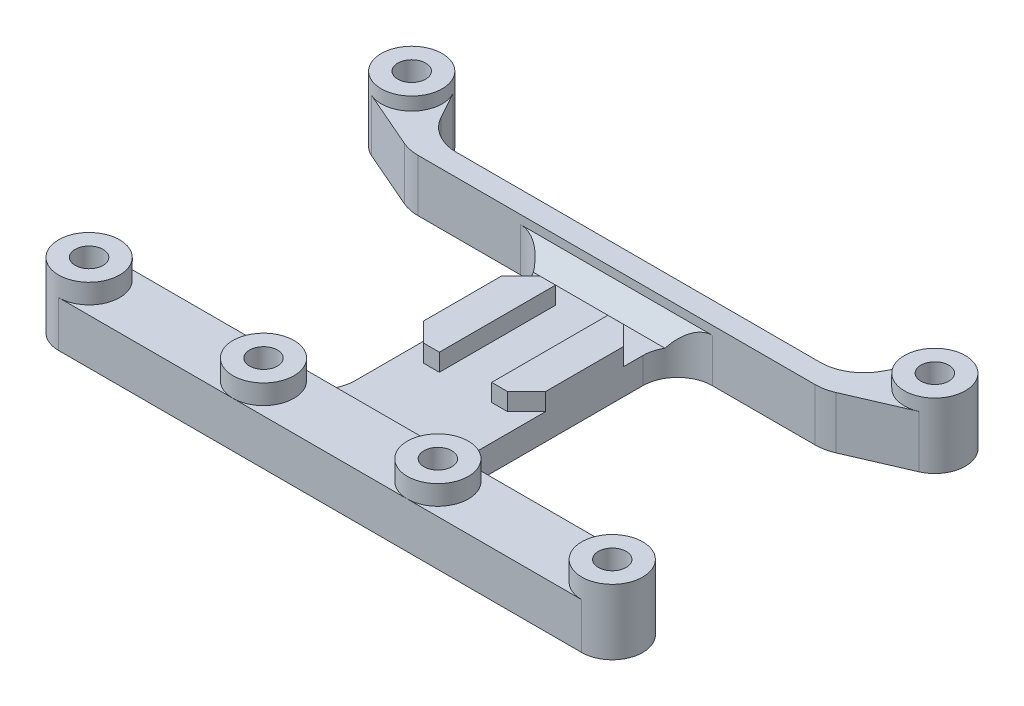
SolidWorks part; units mm, degrees
ref_plane "Front Plane" through (0, 0, 0) normal (0, 0, 1) x (1, 0, 0)
ref_plane "Top Plane" through (0, 0, 0) normal (0, 1, 0) x (1, 0, 0)
ref_plane "Right Plane" through (0, 0, 0) normal (1, 0, 0) x (0, 0, -1)
sketch "Sketch1" plane through (0, 0, 0) normal (0, 1, 0) x (1, 0, 0)
  line L3 (0, 3.5) -> (0, 33) construction
  line L4 (30, 3.5) -> (11, 3.5)
  line L5 (-30, -3.5) -> (30, -3.5)
  line L6 (-20.8493, 33.0006) -> (20.8488, 33)
  line L7 (7, 7.5) -> (7, 26.5002)
  line L8 (-7, 7.5) -> (-7, 26.5005)
  line L9 (-22.7685, 30.5006) -> (-10.9999, 30.5005)
  line L10 (-25.2301, 35.5907) -> (-26.9334, 38.687)
  line L11 (-24.7567, 30.913) -> (-31.3917, 33.7886)
  line L12 (24.7553, 30.9124) -> (31.3917, 33.7886)
  line L13 (25.2298, 35.5901) -> (26.9334, 38.687)
  line L14 (11.0001, 30.5002) -> (22.7669, 30.5)
  line L15 (-11, 3.5) -> (-30, 3.5)
  circle A2 centre (-30, 0) radius 1.6
  circle A3 centre (-10, 0) radius 1.6
  circle A4 centre (10, 0) radius 1.6
  circle A5 centre (30, 0) radius 1.6
  arc A6 (-26.9334, 38.687) -> (-31.3917, 33.7886) centre (-30, 37) ccw
  arc A7 (30, -3.5) -> (30, 3.5) centre (30, 0) ccw
  arc A8 (-30, 3.5) -> (-30, -3.5) centre (-30, 0) ccw
  arc A9 (31.3917, 33.7886) -> (26.9334, 38.687) centre (30, 37) ccw
  arc A10 (24.7553, 30.9124) -> (22.7669, 30.5) centre (22.767, 35.5) cw
  arc A11 (25.2298, 35.5901) -> (20.8488, 33) centre (20.8489, 38) cw
  arc A12 (-24.7567, 30.913) -> (-22.7685, 30.5006) centre (-22.7684, 35.5006) ccw
  arc A13 (-25.2301, 35.5907) -> (-20.8493, 33.0006) centre (-20.8492, 38.0006) ccw
  arc A14 (7, 26.5002) -> (11.0001, 30.5002) centre (11, 26.5002) cw
  arc A15 (-7, 26.5005) -> (-10.9999, 30.5005) centre (-11, 26.5005) ccw
  arc A16 (11, 3.5) -> (7, 7.5) centre (11, 7.5) cw
  arc A17 (-11, 3.5) -> (-7, 7.5) centre (-11, 7.5) ccw
  circle A18 centre (-30, 37) radius 1.6
  circle A19 centre (30, 37) radius 1.6
  point P28 (-0.0002, 33.0003)
  dimension "D5" = 3.2
  dimension "D6" = 5
  dimension "D7" = 4
  dimension "D4" = 20
extrude "Boss-Extrude1" add sketch "Sketch1" along normal blind 3
sketch "Sketch2" plane through (0, 3, 0) normal (0, 1, 0) x (1, 0, 0)
  circle A0 centre (-30, 0) radius 3.5
  circle A1 centre (-10, 0) radius 3.5
  circle A2 centre (10, 0) radius 3.5
  circle A3 centre (30, 0) radius 3.5
  circle A4 centre (-30, 0) radius 1.6
  circle A5 centre (-10, 0) radius 1.6
  circle A6 centre (10, 0) radius 1.6
  circle A7 centre (30, 0) radius 1.6
  circle A8 centre (30, 37) radius 3.5
  circle A9 centre (-30, 37) radius 3.5
  circle A10 centre (-30, 37) radius 1.6
  circle A11 centre (30, 37) radius 1.6
  point P21 (-30, 0)
  dimension "D1" = 3.2
extrude "Boss-Extrude2" add sketch "Sketch2" along normal blind 4.5
sketch "Sketch3" plane through (0, 3, 0) normal (0, 1, 0) x (1, 0, 0)
  line L0 (-7, 26.5005) -> (-7, 7.5) construction
  line L1 (-7, 13.1708) -> (-3, 13.1708)
  line L2 (-7, 13.1708) -> (-7, 26.5002)
  line L3 (-7, 26.5002) -> (-3, 26.5002)
  line L4 (7, 13.1708) -> (7, 26.5002)
  line L5 (-3, 13.1708) -> (-3, 26.5002)
  line L34 (3, 13.1708) -> (3, 26.5002)
  line L35 (3, 26.5002) -> (7, 26.5002)
  line L36 (3, 13.1708) -> (7, 13.1708)
  dimension "D1" = 4
  dimension "D2" = 4
extrude "Boss-Extrude3" add sketch "Sketch3" along normal blind 2
sketch "Sketch4" plane through (0, 3, 0) normal (0, 1, 0) x (1, 0, 0)
  line L10 (11.0001, 30.5002) -> (22.7669, 30.5) construction
  line L11 (24.7553, 30.9124) -> (31.3917, 33.7886) construction
  line L12 (26.9334, 38.687) -> (25.2298, 35.5901) construction
  line L14 (-25.2301, 35.5907) -> (-26.9334, 38.687) construction
  line L15 (-31.3917, 33.7886) -> (-24.7567, 30.913) construction
  line L16 (-22.7685, 30.5006) -> (-10.9999, 30.5005) construction
  line L29 (24.7553, 30.9124) -> (31.3917, 33.7886)
  line L30 (26.9334, 38.687) -> (25.2298, 35.5901)
  line L31 (11.0001, 30.5002) -> (22.7669, 30.5)
  line L32 (-22.7685, 30.5006) -> (-10.9999, 30.5005)
  line L33 (-31.3917, 33.7886) -> (-24.7567, 30.913)
  line L34 (-20.8493, 33.0006) -> (-10.9999, 33.0006)
  line L35 (-25.2301, 35.5907) -> (-26.9334, 38.687)
  line L36 (11.0001, 33) -> (20.8488, 33)
  line L37 (-10.9999, 33.0006) -> (11.0001, 33)
  line L38 (11.0001, 30.5002) -> (-10.9999, 30.5005)
  arc A1 (22.7669, 30.5) -> (24.7553, 30.9124) centre (22.767, 35.5) ccw construction
  arc A3 (20.8488, 33) -> (25.2298, 35.5901) centre (20.8489, 38) ccw construction
  arc A4 (-25.2301, 35.5907) -> (-20.8493, 33.0006) centre (-20.8492, 38.0006) ccw construction
  arc A6 (-24.7567, 30.913) -> (-22.7685, 30.5006) centre (-22.7684, 35.5006) ccw construction
  circle A14 centre (-30, 37) radius 3.5 construction
  circle A15 centre (30, 37) radius 3.5 construction
  arc A16 (-31.3917, 33.7886) -> (-26.9334, 38.687) centre (-30, 37) ccw
  arc A17 (26.9334, 38.687) -> (31.3917, 33.7886) centre (30, 37) ccw
  arc A18 (22.7669, 30.5) -> (24.7553, 30.9124) centre (22.767, 35.5) ccw
  arc A19 (20.8488, 33) -> (25.2298, 35.5901) centre (20.8489, 38) ccw
  arc A20 (-24.7567, 30.913) -> (-22.7685, 30.5006) centre (-22.7684, 35.5006) ccw
  arc A21 (-25.2301, 35.5907) -> (-20.8493, 33.0006) centre (-20.8492, 38.0006) ccw
extrude "Boss-Extrude4" add sketch "Sketch4" along normal blind 3
chamfer "Chamfer1" distance 2.2 angle 45 4 edges at (-7, 4, -26.5002) (7, 4, -26.5002) (7, 4, -13.1708) (-7, 4, -13.1708)
sketch "Sketch5" plane through (0, 3, 0) normal (0, 1, 0) x (1, 0, 0)
  line L47 (-30, 3.5) -> (30, 3.5)
  line L49 (-30, -3.5) -> (30, -3.5)
  circle A16 centre (-10, 0) radius 3.5 construction
  circle A17 centre (-10, 0) radius 3.5
  circle A18 centre (10, 0) radius 3.5 construction
  circle A19 centre (10, 0) radius 3.5
  arc A20 (-30, -3.5) -> (-30, 3.5) centre (-30, 0) ccw construction
  arc A21 (-30, -3.5) -> (-30, 3.5) centre (-30, 0) ccw
  circle A22 centre (30, 0) radius 3.5 construction
  arc A23 (30, 3.5) -> (30, -3.5) centre (30, 0) ccw
  line M14 (-11, 3.5) -> (-30, 3.5)
  arc M15 (-30, 3.5) -> (-30, -3.5) centre (-30, 0) cw
  line M16 (-30, -3.5) -> (-10, -3.5)
  circle M17 centre (-10, 0) radius 3.5
  line M18 (-10, -3.5) -> (10, -3.5)
  circle M19 centre (10, 0) radius 3.5
  line M20 (10, -3.5) -> (30, -3.5)
  arc M21 (30, -3.5) -> (30, 3.5) centre (30, 0) cw
  line M22 (30, 3.5) -> (11, 3.5)
extrude "Boss-Extrude5" add sketch "Sketch5" along normal blind 2.25 contours L47 M14 M15 M16 M17 | L47 M17 M18 M19 | L47 M19 M20 M21 M22 region at (-20, 3, 0) region at (0, 3, 0) region at (20, 3, 0)
chamfer "Chamfer2" distance 2 angle 45 2 edges at (0, 3, -3.5) (0.0001, 3, -30.5003)
